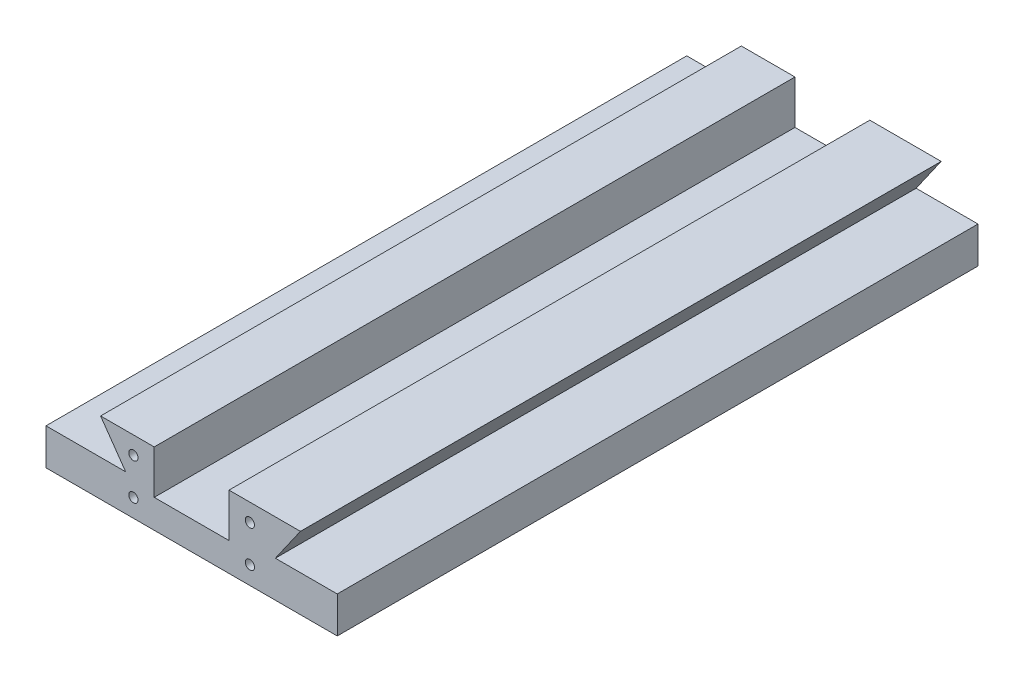
SolidWorks part; units mm, degrees
material "Ductile Iron"
ref_plane "Front Plane" through (0, 0, 0) normal (0, 0, 1) x (1, 0, 0)
ref_plane "Top Plane" through (0, 0, 0) normal (0, 1, 0) x (1, 0, 0)
ref_plane "Right Plane" through (0, 0, 0) normal (1, 0, 0) x (0, 0, -1)
sketch "dovetail-male-profile" plane through (0, 0, 0) normal (0, 0, 1) x (1, 0, 0)
  line L0 (47.4471, 31.496) -> (16.3103, 31.496)
  line L1 (-16.3103, 31.496) -> (-39.6952, 31.496)
  line L2 (16.3103, 31.496) -> (16.3103, 12.446)
  line L3 (16.3103, 12.446) -> (-16.3103, 12.446)
  line L4 (-16.3103, 12.446) -> (-16.3103, 31.496)
  point P7 (0, 12.446)
  line B0 (-63.5, 0) -> (63.5, 0)
  line B1 (63.5, 0) -> (63.5, 15.875)
  line B2 (63.5, 15.875) -> (36.5092, 15.875)
  line B3 (36.5092, 15.875) -> (47.625, 31.75)
  line B4 (47.625, 31.75) -> (16.0563, 31.75)
  line B5 (-39.8731, 31.75) -> (-28.7573, 15.875)
  line B6 (-28.7573, 15.875) -> (-63.5, 15.875)
  line B7 (-63.5, 15.875) -> (-63.5, 0)
  line B8 (-36.5092, 15.875) -> (-47.625, 31.75)
  line B9 (-47.625, 31.75) -> (-39.8731, 31.75)
  line B10 (-16.0563, 31.75) -> (-16.0563, 12.7)
  line B11 (-16.0563, 12.7) -> (16.0563, 12.7)
  line B12 (16.0563, 12.7) -> (16.0563, 31.75)
  line B13 (-16.0563, 31.75) -> (-39.8731, 31.75)
  line B14 (-63.5, 15.875) -> (-63.5, 47.625)
  line B15 (-63.5, 47.625) -> (63.5, 47.625)
  line B16 (63.5, 47.625) -> (63.5, 15.875)
  line B17 (-16.0563, 31.75) -> (16.0563, 31.75)
  line B18 (0, 47.625) -> (0, 0) construction
  line B19 (-36.5092, 15.875) -> (36.5092, 15.875) construction
  line B20 (-28.702, 36.957) -> (28.702, 36.957) construction
  line B21 (-25.4, 7.874) -> (25.4, 7.874) construction
  line B22 (-25.4, 7.874) -> (-25.4, 23.8125) construction
  line B23 (25.4, 7.874) -> (25.4, 23.8125) construction
  line B24 (-52.832, 23.8125) -> (52.832, 23.8125) construction
  circle B25 centre (0, 22.225) radius 18.669 construction
  dimension "D1" = 0.254
  dimension "D2" = 0.254
  dimension "D3" = 0.254
sketch_block_instance "dovetail pair-1"
sketch_block "dovetail pair" parameters "D8"=37.338, "D1"=55, "D2"=127, "D3"=6.35, "D4"=15.875, "D5"=31.75, "D6"=95.25, "D7"=19.05, "D9"=55, "D10"=31.75, "D11"=50.8, "D12"=23.876, "D13"=7.874, "D14"=10.668, "D15"=34.798, "D16"=21.082, "D17"=7.9375
extrude "x-guide-extrude" add sketch "dovetail-male-profile" along normal blind 279.4 contours B10 B13 B5 B6 B7 B0 B1 B2 B3 B4 B12 B11 region at (1.7848, 11.9878, 0)
hole_wizard "end plate holes" positions "Sketch2" profile "Sketch3" tap size "#10-32" standard "ANSI Inch"
sketch "Sketch2" plane through (0, 0, 0) normal (0, 0, -1) x (-1, 0, 0)
  point P27 (-25.4, 23.8125)
  point P29 (25.4, 23.8125)
  point P31 (25.4, 7.874)
  point P33 (-25.4, 7.874)
sketch "Sketch3" plane through (25.4, 23.8125, 0) normal (1, 0, 0) x (0, 1, 0)
  line L0 (0, 0) -> (0, 13.1513)
  line L1 (0, 13.1513) -> (2.0193, 11.938)
  line L2 (2.0193, 11.938) -> (2.0193, 0)
  line L3 (2.0193, 0) -> (0, 0)
  line L4 (0, 13.1513) -> (-2.0193, 11.938) construction
  line L5 (0, -6.35) -> (0, 107.95) construction
  dimension "Tap Drill Dia." = 4.0386
  dimension "Tap Drill Depth" = 11.938
  dimension "Drill Angle" = 118
cosmetic thread "Hole Thread1" parameters "D1"=9.652, "D2"=4.826
cosmetic thread "Hole Thread2" parameters "D1"=9.652, "D2"=4.826
cosmetic thread "Hole Thread9" parameters "D1"=9.652, "D2"=4.826
cosmetic thread "Hole Thread10" parameters "D1"=9.652, "D2"=4.826
hole_wizard "end plate holes 2" positions "Sketch4" profile "Sketch5" tap size "#10-32" standard "ANSI Inch"
sketch "Sketch4" plane through (0, 0, 279.4) normal (0, 0, 1) x (1, 0, 0)
  point P8 (25.4, 23.8125)
  point P10 (25.4, 7.874)
  point P12 (-25.4, 7.874)
  point P14 (-25.4, 23.8125)
cosmetic thread "Hole Thread5" parameters "D1"=9.652, "D2"=4.826
cosmetic thread "Hole Thread6" parameters "D1"=9.652, "D2"=4.826
cosmetic thread "Hole Thread11" parameters "D1"=9.652, "D2"=4.826
cosmetic thread "Hole Thread12" parameters "D1"=9.652, "D2"=4.826
sketch "Sketch5" plane through (25.4, 23.8125, 279.4) normal (1, 0, 0) x (0, -1, 0)
  line L0 (0, 0) -> (0, 13.1513)
  line L1 (0, 13.1513) -> (2.0193, 11.938)
  line L2 (2.0193, 11.938) -> (2.0193, 0)
  line L5 (2.0193, 0) -> (0, 0)
  line L10 (0, 13.1513) -> (-2.0193, 11.938) construction
  line L11 (0, -6.35) -> (0, 107.95) construction
  dimension "Tap Drill Dia." = 4.0386
  dimension "Tap Drill Depth" = 11.938
  dimension "Drill Angle" = 118
equation "\"dovetail-angle\" = 55"
equation "\"dovetail-stock-width\" = 5"
equation "\"dovetail-stock-height\" = 1.25"
equation "\"D1@dovetail-male-profile\"=0.01"
equation "\"dovetail-throat-width\" = \"dovetail-stock-width\" - (2 * \"dovetail-depth\")"
equation "\"D3@dovetail-male-profile\"=.01"
equation "\"dovetail-depth\" = 0.5 * \"dovetail-stock-height\""
equation "\"D2@dovetail-male-profile\"=.01"
equation "\"delta-x\" = 6"
equation "\"delta-y\" = 3"
equation "\"gib-thickness\" = 0.25"
equation "\"x-slide-length\" = \"dovetail-stock-width\" + \"delta-x\""
equation "\"y-slide-length\" = \"dovetail-stock-width\" + \"delta-y\""
equation "\"D1@x-guide-extrude\"=\"x-slide-length\""
equation "\"dog-point-diam\" = .149"
equation "\"dog-point-length\" = .067"
equation "\"dovetail-double-height\" = 2 * \"dovetail-depth\" + 0.5"
equation "\"acme-major-diam\" = .5"
equation "\"acme-pitch-diam\" = 0.45"
equation "\"acme-minor-diam\" = 0.4"
equation "\"acme-nut-od\" = 1.47"
equation "\"acme-nut-length\" = 1"
equation "\"acme-nut-trim-height\" = .75"
equation "\"screw-bearing-od\" = 0.5"
equation "\"screw-bearing-length\" = .375"
equation "\"end-plate-thickness\" = \"screw-bearing-length\""
equation "\"screw-bearing-id\" = .375"
equation "\"screw-add-length\" = 2 * \"end-plate-thickness\" + 1 + 0.5"
equation "\"acme-nut-mount-hole-space-horz\" = 0.95"
equation "\"acme-nut-mount-hole-space-vert\" = 0.5 * \"acme-nut-length\""
equation "\"x-screw-length\" = \"x-slide-length\" + \"screw-add-length\""
equation "\"y-screw-length\" = \"y-slide-length\" + \"screw-add-length\""
equation "\"D2@dovetail pair\"=\"dovetail-stock-width\""
equation "\"D1@dovetail pair\"=\"dovetail-angle\""
equation "\"D3@dovetail pair\"=\"gib-thickness\""
equation "\"D4@dovetail pair\"=\"dovetail-depth\""
equation "\"D5@dovetail pair\"=\"dovetail-stock-height\""
equation "\"D6@dovetail pair\"=\"dovetail-throat-width\""
equation "\"D10@dovetail pair\"=\"dovetail-stock-height\""
equation "\"D7@dovetail pair\"=\"acme-nut-trim-height\""
equation "\"D8@dovetail pair\"=\"acme-nut-od\""
equation "\"D9@dovetail pair\"=\"dovetail-angle\""
equation "\"D17@dovetail pair\"=\"dovetail-depth\"/2"
